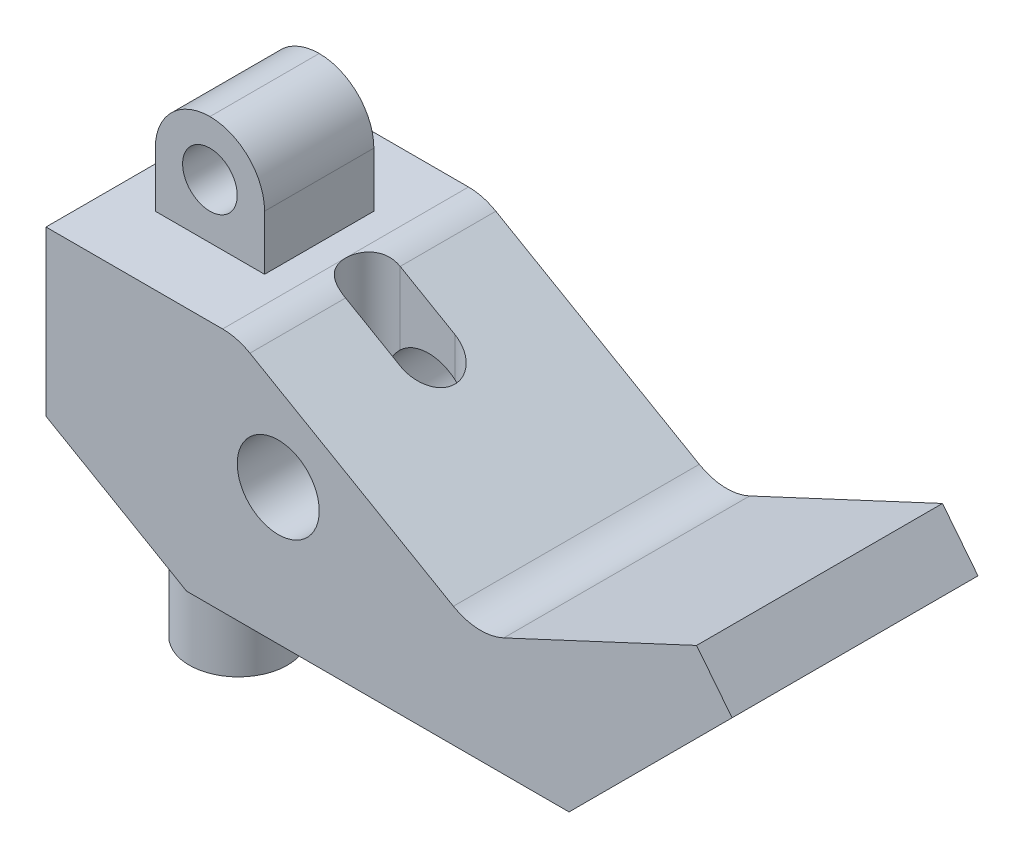
SolidWorks part; units mm, degrees
ref_plane "Front Plane" through (0, 0, 0) normal (0, 0, 1) x (1, 0, 0)
ref_plane "Top Plane" through (0, 0, 0) normal (0, 1, 0) x (1, 0, 0)
ref_plane "Right Plane" through (0, 0, 0) normal (1, 0, 0) x (0, 0, -1)
sketch "Sketch1" plane through (0, 0, 0) normal (0, 0, 1) x (1, 0, 0)
  line L11 (0, 0) -> (70, 0)
  line L12 (0, 0) -> (-25.7202, 14.8495)
  line L13 (-25.7202, 14.8495) -> (-25.7202, 44.8495)
  line L14 (-25.7202, 44.8495) -> (9.2798, 44.8495)
  line L15 (9.2798, 44.8495) -> (48.8302, 22.0151)
  line L16 (58.0564, 21.6123) -> (93.3384, 38.0646)
  line L17 (70, 0) -> (99.8385, 29.8385)
  line L18 (99.8385, 29.8385) -> (93.3384, 38.0646)
  arc A0 (58.0564, 21.6123) -> (48.8302, 22.0151) centre (53.8302, 30.6754) cw
  point P9 (53.3384, 19.4123)
  dimension "D6" = 10
  dimension "D1" = 70
  dimension "D2" = 210
  dimension "D3" = 30
  dimension "D4" = 35
  dimension "D5" = 40
  dimension "D7" = 125
extrude "Boss-Extrude1" add sketch "Sketch1" along normal blind 45
sketch "Sketch2" plane through (0, 44.8495, 0) normal (0, 1, 0) x (1, 0, 0)
  line L0 (-25.7202, -45) -> (-25.7202, 0) construction
  line L1 (-18.2202, -12.5) -> (1.7798, -12.5)
  line L2 (-18.2202, -12.5) -> (-18.2202, -32.5)
  line L3 (-18.2202, -32.5) -> (1.7798, -32.5)
  line L4 (1.7798, -12.5) -> (1.7798, -32.5)
  line L5 (9.2798, 0) -> (-25.7202, 0) construction
  dimension "D1" = 20
  dimension "D2" = 20
  dimension "D3" = 7.5
  dimension "D4" = 12.5
extrude "Boss-Extrude3" add sketch "Sketch2" along normal blind 20
fillet "Fillet2" radius 10 2 edges at (1.7798, 64.8495, 22.5) (-18.2202, 64.8495, 22.5)
fillet "Fillet3" radius 10 1 edges at (9.2798, 44.8495, 22.5)
sketch "Sketch3" plane through (0, 0, 32.5) normal (0, 0, 1) x (1, 0, 0)
  circle A0 centre (-8.2202, 54.8495) radius 5
extrude "Cut-Extrude1" cut sketch "Sketch3" against normal blind 20
ref_plane "Plane1" through (0, 14.8495, 0) normal (0, 1, 0) x (1, 0, 0)
sketch "Sketch4" plane through (0, 14.8495, 0) normal (0, 1, 0) x (1, 0, 0)
  line L0 (-25.7202, -45) -> (-25.7202, 0) construction
  line L1 (-25.7202, -45) -> (0, -45) construction
  circle A0 centre (-13.0202, -22.5) radius 12.7
  dimension "D1" = 12.7
  dimension "D2" = 22.5
extrude "Boss-Extrude4" add sketch "Sketch4" against normal up to surface (14.8495 mm away) up to face at (35, 0, 22.5)
sketch "Sketch6" plane through (0, 0, 0) normal (0, -1, 0) x (1, 0, 0)
  circle A0 centre (-13.0202, 22.5) radius 9
  circle A1 centre (-13.0202, 22.5) radius 12.7 construction
  dimension "D2" = 18
  dimension "D1" = 0
extrude "Boss-Extrude5" add sketch "Sketch6" along normal blind 25
sketch "Sketch7" plane through (0, 44.8495, 0) normal (0, 1, 0) x (1, 0, 0)
  line L0 (11.6003, -22.5) -> (21.6003, -22.5) construction
  line L1 (11.6003, -17.5) -> (21.6003, -17.5)
  line L2 (11.6003, -27.5) -> (21.6003, -27.5)
  line L3 (48.8302, -45) -> (11.6003, -45) construction
  line L4 (6.6003, -45) -> (6.6003, 0) construction
  arc A0 (11.6003, -17.5) -> (11.6003, -27.5) centre (11.6003, -22.5) ccw
  arc A1 (21.6003, -27.5) -> (21.6003, -17.5) centre (21.6003, -22.5) ccw
  point P2 (16.6003, -22.5)
  dimension "D1" = 10
  dimension "D2" = 10
  dimension "D3" = 22.5
  dimension "D4" = 5
extrude "Cut-Extrude2" cut sketch "Sketch7" against normal blind 55
sketch "Sketch8" plane through (0, 0, 45) normal (0, 0, 1) x (1, 0, 0)
  line L0 (-25.7202, 44.8495) -> (-25.7202, 14.8495) construction
  line L1 (6.6003, 44.8495) -> (-25.7202, 44.8495) construction
  circle A0 centre (16.7798, 24.8495) radius 7.5
  dimension "D1" = 42.5
  dimension "D3" = 15
  dimension "D2" = 20
extrude "Cut-Extrude3" cut sketch "Sketch8" against normal blind 55
